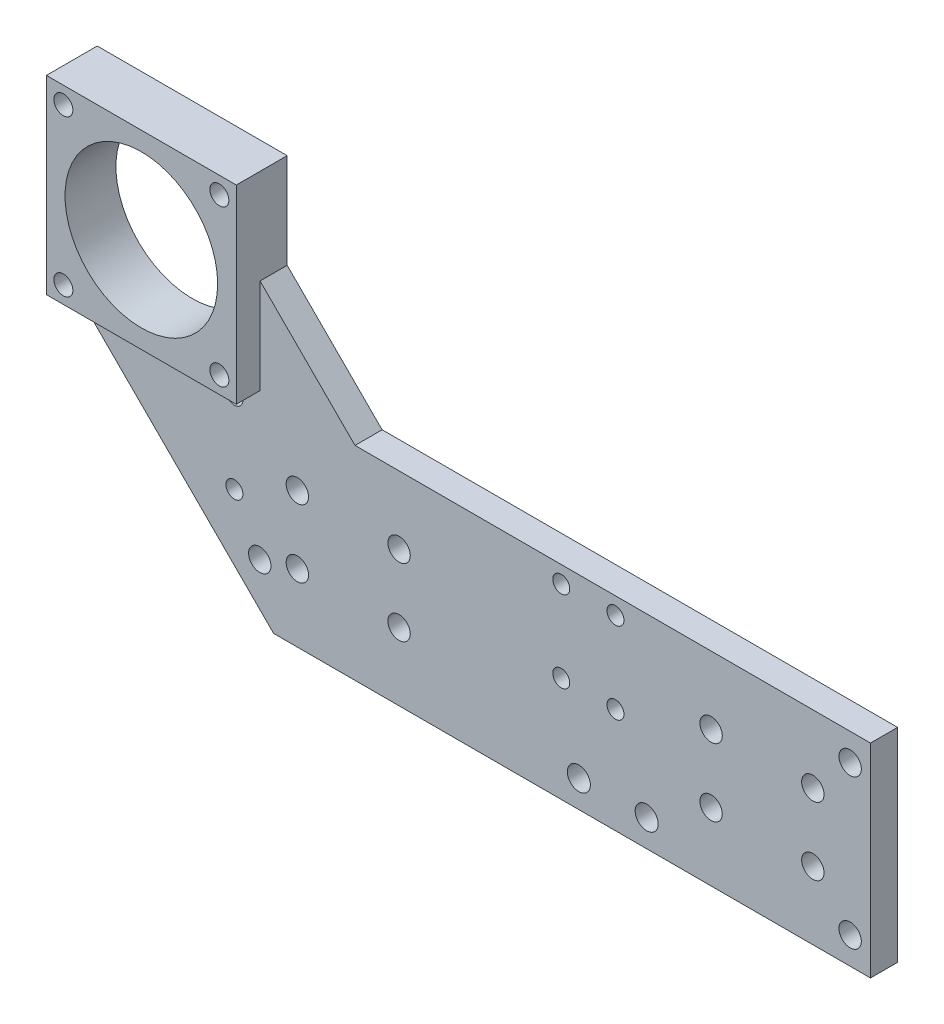
SolidWorks part; units mm, degrees
ref_plane "前视基准面" through (0, 0, 0) normal (0, 0, 1) x (1, 0, 0)
ref_plane "上视基准面" through (0, 0, 0) normal (0, 1, 0) x (1, 0, 0)
ref_plane "右视基准面" through (0, 0, 0) normal (1, 0, 0) x (0, 0, -1)
other "Configuration Table"
sketch "草图1" plane through (0, 0, 0) normal (0, 0, 1) x (1, 0, 0)
  line L1 (-56, -29) -> (56, -29)
  line L2 (-56, -29) -> (-56, 29)
  line L3 (-56, 29) -> (56, 29)
  line L4 (56, -29) -> (56, 29)
  line L5 (-56, -29) -> (56, 29) construction
  line L6 (-56, 29) -> (56, -29) construction
  point P0 (0, 0)
  dimension "D1" = 112
  dimension "D2" = 58
extrude "凸台-拉伸1" add sketch "草图1" along normal blind 4
sketch "草图2" plane through (0, 0, 4) normal (0, 0, 1) x (1, 0, 0)
  line L0 (56, 1) -> (-14, 1)
  line L1 (56, -29) -> (56, 29) construction
  line L3 (56, 29) -> (-56, 29) construction
  line L4 (-28, 29) -> (-56, 29)
  line L5 (-56, 29) -> (-56, 1)
  line L6 (-56, 29) -> (-56, -29) construction
  line L7 (-56, 1) -> (-26, -29)
  line L8 (-56, -29) -> (56, -29) construction
  line L9 (-26, -29) -> (56, -29)
  line L10 (56, -29) -> (56, 1)
  line L11 (-28, 29) -> (-28, 15)
  line L12 (-14, 1) -> (-28, 15)
  dimension "D1" = 45
extrude "切除-拉伸1" cut sketch "草图2" against normal blind 4 flip side to cut
sketch "草图3" plane through (0, 0, 4) normal (0, 0, 1) x (1, 0, 0)
  circle A0 centre (-42, 15) radius 11.25
  dimension "D1" = 22.5
extrude "切除-拉伸2" cut sketch "草图3" against normal blind 4
sketch "草图4" plane through (0, 0, 4) normal (0, 0, 1) x (1, 0, 0)
  circle A0 centre (-22.5, -19) radius 1.65
  circle A1 centre (-22.5, -9) radius 1.65
  circle A2 centre (-7.5, -19) radius 1.65
  circle A3 centre (-7.5, -9) radius 1.65
  circle A4 centre (38.5, -19) radius 1.65
  circle A5 centre (38.5, -9) radius 1.65
  circle A6 centre (53.5, -19) radius 1.65
  circle A7 centre (53.5, -9) radius 1.65
  circle A10 centre (19, -25) radius 1.7
  circle A11 centre (29, -25) radius 1.7
  dimension "D1" = 3.3
  dimension "D2" = 3.4
extrude "切除-拉伸3" cut sketch "草图4" against normal up to next
sketch "草图5" plane through (0, 0, 0) normal (0, 0, -1) x (-1, 0, 0)
  circle A0 centre (-16.406, -13.5) radius 1.25
  circle A1 centre (-24.406, -13.5) radius 1.25
  circle A2 centre (-16.406, -1.5) radius 1.25
  circle A3 centre (-24.406, -1.5) radius 1.25
  circle A4 centre (31.7799, -13.5) radius 1.25
  circle A5 centre (31.7799, -1.5) radius 1.25
  dimension "D1" = 2.5
extrude "切除-拉伸4" cut sketch "草图5" against normal up to next
sketch "草图6" plane through (56, 0, 0) normal (1, 0, 0) x (0, 0, -1)
  line L0 (0, -29) -> (0, 1) construction
  line L1 (0, -29) -> (-4, -29)
  line L2 (0, -29) -> (0, 1)
  line L3 (0, 1) -> (-4, 1)
  line L4 (-4, -29) -> (-4, 1)
  line L5 (-4, 1) -> (-4, 15) construction
sketch "草图8" plane through (0, 0, 0) normal (0, 0, -1) x (-1, 0, 0)
  line L0 (-56, -29) -> (-56, 1) construction
  line L1 (-56, 1) -> (-62, 1)
  line L2 (-56, 1) -> (-56, -29)
  line L3 (-56, -29) -> (-62, -29)
  line L4 (-62, 1) -> (-62, -29)
  dimension "D1" = 6
extrude "凸台-拉伸3" add sketch "草图8" against normal blind 4
sketch "草图10" plane through (0, 0, 4) normal (0, 0, 1) x (1, 0, 0)
  line L1 (62, 1) -> (62, -29) construction
  line L2 (-26, -29) -> (62, -29) construction
  line L3 (62, 1) -> (-14, 1) construction
  circle A0 centre (59, -25) radius 1.65
  circle A1 centre (59, -3) radius 1.65
  dimension "D1" = 3.3
  dimension "D2" = 3.3
  dimension "D3" = 3
  dimension "D4" = 3
  dimension "D5" = 4
  dimension "D6" = 4
extrude "切除-拉伸5" cut sketch "草图10" against normal up to next
sketch "草图11" plane through (0, 0, 4) normal (0, 0, 1) x (1, 0, 0)
  circle A0 centre (-28.0366, -20.5937) radius 1.65
  dimension "D1" = 3.3
extrude "切除-拉伸6" cut sketch "草图11" against normal up to next
sketch "草图13" plane through (0, 0, 0) normal (0, 0, -1) x (-1, 0, 0)
  line L1 (30.5, 26.5) -> (53.5, 26.5) construction
  line L2 (30.5, 26.5) -> (30.5, 3.5) construction
  line L3 (30.5, 3.5) -> (53.5, 3.5) construction
  line L4 (53.5, 26.5) -> (53.5, 3.5) construction
  line L5 (30.5, 26.5) -> (53.5, 3.5) construction
  line L6 (30.5, 3.5) -> (53.5, 26.5) construction
  circle A0 centre (53.5, 26.5) radius 1.4
  circle A1 centre (53.5, 3.5) radius 1.4
  circle A2 centre (30.5, 3.5) radius 1.4
  circle A3 centre (30.5, 26.5) radius 1.4
  point P0 (42, 15)
  dimension "D3" = 2.8
  dimension "D1" = 23
  dimension "D2" = 23
extrude "切除-拉伸7" cut sketch "草图13" against normal through all
sketch "草图14" plane through (0, 0, 4) normal (0, 0, 1) x (1, 0, 0)
  line L1 (-56, 29) -> (-28, 29)
  line L2 (-56, 29) -> (-56, 1)
  line L3 (-56, 1) -> (-28, 1)
  line L4 (-28, 29) -> (-28, 1)
  circle A0 centre (-42, 15) radius 11.25
  circle A1 centre (-30.5, 26.5) radius 1.4
  circle A2 centre (-53.5, 26.5) radius 1.4
  circle A3 centre (-53.5, 3.5) radius 1.4
  circle A4 centre (-30.5, 3.5) radius 1.4
extrude "凸台-拉伸4" add sketch "草图14" along normal blind 3.5
